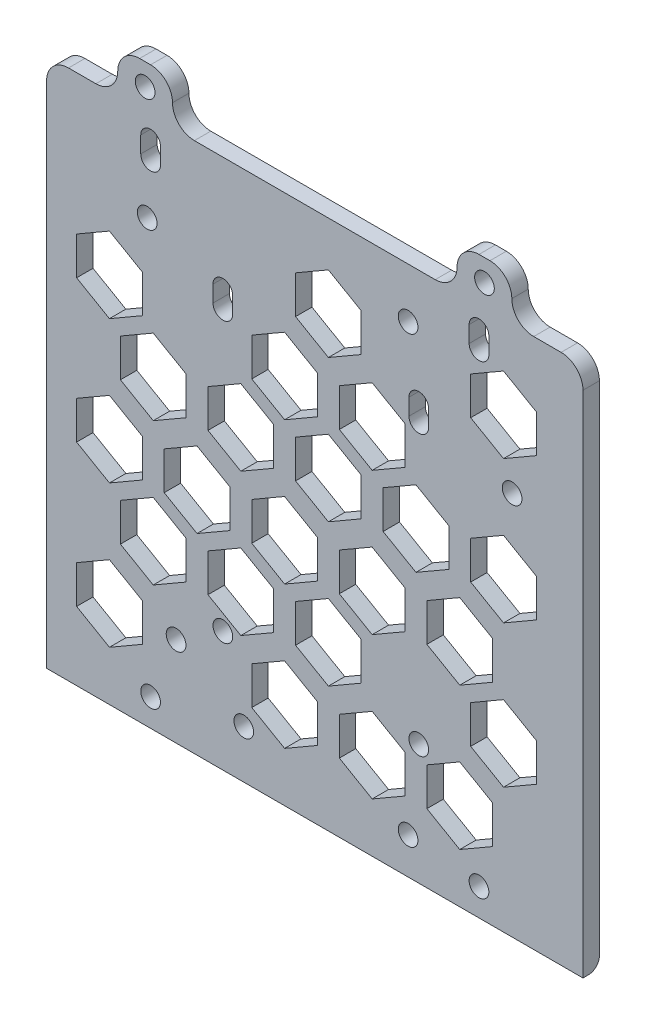
SolidWorks part; units mm, degrees
material "PLA 100% Infill"
ref_plane "Front Plane" through (0, 0, 0) normal (0, 0, 1) x (1, 0, 0)
ref_plane "Top Plane" through (0, 0, 0) normal (0, 1, 0) x (1, 0, 0)
ref_plane "Right Plane" through (0, 0, 0) normal (1, 0, 0) x (0, 0, -1)
sketch "Sketch1" plane through (0, 0, 0) normal (0, 0, 1) x (1, 0, 0)
  line L0 (-49, 97) -> (-49, 0) construction
  line L1 (0, 0) -> (-98, 0)
  line L2 (0, 0) -> (0, 97)
  line L3 (0, 97) -> (-98, 97)
  line L4 (-98, 0) -> (-98, 97)
  line L5 (-80, 101) -> (-18, 101) construction
  line L6 (-98, 97) -> (-75, 97)
  line L8 (-85, 105) -> (-75, 105)
  line L9 (-75, 97) -> (-75, 105)
  line L10 (0, 97) -> (-23, 97)
  line L12 (-13, 105) -> (-23, 105)
  line L13 (-23, 97) -> (-23, 105)
  line L14 (-80, 105) -> (-80, 101) construction
  line L15 (-85, 105) -> (-85, 97)
  line L16 (-80.8, 93) -> (-80.8, 90)
  line L17 (-13, 105) -> (-13, 97)
  line L18 (-18, 105) -> (-18, 101) construction
  line L19 (-77.2, 90) -> (-77.2, 93)
  line L20 (-20.8, 90) -> (-20.8, 93)
  line L21 (-17.2, 93) -> (-17.2, 90)
  line L22 (-19, 91.5) -> (-19, 5) construction
  line L23 (-30, 22) -> (-65.8, 22) construction
  line L24 (-65.8, 76) -> (-65.8, 22) construction
  line L25 (-30, 76) -> (-30, 22) construction
  line L26 (-67.6, 76) -> (-67.6, 73)
  line L27 (-64, 76) -> (-64, 73)
  line L28 (-31.8, 76) -> (-31.8, 73)
  line L29 (-28.2, 76) -> (-28.2, 73)
  circle A0 centre (-79, 5) radius 1.8
  circle A1 centre (-19, 5) radius 1.8
  circle A2 centre (-19, 91.5) radius 1.8
  circle A3 centre (-79, 91.5) radius 1.8
  circle A4 centre (-80, 101) radius 1.8
  circle A5 centre (-18, 101) radius 1.8
  arc A6 (-80.8, 90) -> (-77.2, 90) centre (-79, 90) ccw
  arc A7 (-77.2, 93) -> (-80.8, 93) centre (-79, 93) ccw
  arc A8 (-17.2, 90) -> (-20.8, 90) centre (-19, 90) cw
  arc A9 (-20.8, 93) -> (-17.2, 93) centre (-19, 93) cw
  circle A10 centre (-30, 22) radius 1.8
  circle A11 centre (-65.8, 22) radius 1.8
  circle A12 centre (-65.8, 76) radius 1.8
  circle A13 centre (-30, 76) radius 1.8
  circle A14 centre (-65.8, 73) radius 1.8
  circle A15 centre (-30, 73) radius 1.8
  point P61 (0, 0)
  point P62 (-64, 73)
  point P63 (0, 0)
  point P64 (-28.2, 73)
  point P65 (-30, 76.446)
  dimension "D5" = 3.6
  dimension "D8" = 86.5
  dimension "D9" = 10
  dimension "D10" = 8
  dimension "D4" = 5
  dimension "D11" = 62
  dimension "D12" = 62
  dimension "D15" = 4
  dimension "D16" = 60
  dimension "D17" = 3.6
  dimension "D1" = 98
  dimension "D2" = 97
  dimension "D3" = 60
  dimension "D13" = 1.5
  dimension "D14" = 3
  dimension "D18" = 35.8
  dimension "D19" = 30
  dimension "D20" = 22
  dimension "D22" = 3
  dimension "D23" = 54
  dimension "D6" = 2
  dimension "D7" = 2
  dimension "D21" = 2
extrude "Boss-Extrude1" add sketch "Sketch1" along normal blind 3 contours L3 L9 L8 A4 | L4 L1 L2 L3 A3 A2 A1 A0 | L13 L3 L12 A5 region at (-49.0073, 48.3433, 0) region at (-18, 97.1281, 0) region at (-84.8719, 101, 0)
fillet "Fillet1" radius 4 10 edges at (0, 97, 1.5) (-13, 97, 1.5) (-13, 105, 1.5) (-23, 105, 1.5) (-23, 97, 1.5) (-75, 97, 1.5) (-75, 105, 1.5) (-98, 97, 1.5) (-85, 105, 1.5) (-85, 97, 1.5)
fillet "Fillet2" radius 2 1 edges at (-49, 0, 0)
sketch "Sketch3" plane through (0, 0, 3) normal (0, 0, 1) x (1, 0, 0)
  line L0 (-98, 0) -> (-98, 93) construction
  line L1 (-80.5172, 12.537) -> (-80.5172, 19.4652)
  line L2 (-80.5172, 19.4652) -> (-86.5172, 22.9293)
  line L3 (-86.5172, 22.9293) -> (-92.5172, 19.4652)
  line L4 (-92.5172, 19.4652) -> (-92.5172, 12.537)
  line L5 (-92.5172, 12.537) -> (-86.5172, 9.0729)
  line L6 (-86.5172, 9.0729) -> (-80.5172, 12.537)
  line L14 (-72.5172, 26.3934) -> (-72.5172, 33.3216)
  line L15 (-72.5172, 33.3216) -> (-78.5172, 36.7857)
  line L16 (-78.5172, 36.7857) -> (-84.5172, 33.3216)
  line L17 (-84.5172, 33.3216) -> (-84.5172, 26.3934)
  line L18 (-84.5172, 26.3934) -> (-78.5172, 22.9293)
  line L19 (-78.5172, 22.9293) -> (-72.5172, 26.3934)
  line L25 (-56.5172, 26.3934) -> (-56.5172, 33.3216)
  line L26 (-56.5172, 33.3216) -> (-62.5172, 36.7857)
  line L27 (-62.5172, 36.7857) -> (-68.5172, 33.3216)
  line L28 (-68.5172, 33.3216) -> (-68.5172, 26.3934)
  line L29 (-68.5172, 26.3934) -> (-62.5172, 22.9293)
  line L30 (-62.5172, 22.9293) -> (-56.5172, 26.3934)
  line L31 (-48.5172, 12.537) -> (-48.5172, 19.4652)
  line L32 (-48.5172, 19.4652) -> (-54.5172, 22.9293)
  line L33 (-54.5172, 22.9293) -> (-60.5172, 19.4652)
  line L34 (-60.5172, 19.4652) -> (-60.5172, 12.537)
  line L35 (-60.5172, 12.537) -> (-54.5172, 9.0729)
  line L36 (-54.5172, 9.0729) -> (-48.5172, 12.537)
  line L37 (-40.5172, 26.3934) -> (-40.5172, 33.3216)
  line L38 (-40.5172, 33.3216) -> (-46.5172, 36.7857)
  line L39 (-46.5172, 36.7857) -> (-52.5172, 33.3216)
  line L40 (-52.5172, 33.3216) -> (-52.5172, 26.3934)
  line L41 (-52.5172, 26.3934) -> (-46.5172, 22.9293)
  line L42 (-46.5172, 22.9293) -> (-40.5172, 26.3934)
  line L43 (-32.5172, 12.537) -> (-32.5172, 19.4652)
  line L44 (-32.5172, 19.4652) -> (-38.5172, 22.9293)
  line L45 (-38.5172, 22.9293) -> (-44.5172, 19.4652)
  line L46 (-44.5172, 19.4652) -> (-44.5172, 12.537)
  line L47 (-44.5172, 12.537) -> (-38.5172, 9.0729)
  line L48 (-38.5172, 9.0729) -> (-32.5172, 12.537)
  line L55 (-16.5172, 12.537) -> (-16.5172, 19.4652)
  line L56 (-16.5172, 19.4652) -> (-22.5172, 22.9293)
  line L57 (-22.5172, 22.9293) -> (-28.5172, 19.4652)
  line L58 (-28.5172, 19.4652) -> (-28.5172, 12.537)
  line L59 (-28.5172, 12.537) -> (-22.5172, 9.0729)
  line L60 (-22.5172, 9.0729) -> (-16.5172, 12.537)
  line L61 (-8.5172, 26.3934) -> (-8.5172, 33.3216)
  line L62 (-8.5172, 33.3216) -> (-14.5172, 36.7857)
  line L63 (-14.5172, 36.7857) -> (-20.5172, 33.3216)
  line L64 (-20.5172, 33.3216) -> (-20.5172, 26.3934)
  line L65 (-20.5172, 26.3934) -> (-14.5172, 22.9293)
  line L66 (-14.5172, 22.9293) -> (-8.5172, 26.3934)
  line L67 (-64.5172, 38.537) -> (-64.5172, 45.4652)
  line L68 (-64.5172, 45.4652) -> (-70.5172, 48.9293)
  line L69 (-70.5172, 48.9293) -> (-76.5172, 45.4652)
  line L70 (-76.5172, 45.4652) -> (-76.5172, 38.537)
  line L71 (-76.5172, 38.537) -> (-70.5172, 35.0729)
  line L72 (-70.5172, 35.0729) -> (-64.5172, 38.537)
  line L73 (-56.5172, 52.3934) -> (-56.5172, 59.3216)
  line L74 (-56.5172, 59.3216) -> (-62.5172, 62.7857)
  line L75 (-62.5172, 62.7857) -> (-68.5172, 59.3216)
  line L76 (-68.5172, 59.3216) -> (-68.5172, 52.3934)
  line L77 (-68.5172, 52.3934) -> (-62.5172, 48.9293)
  line L78 (-62.5172, 48.9293) -> (-56.5172, 52.3934)
  line L79 (-48.5172, 38.537) -> (-48.5172, 45.4652)
  line L80 (-48.5172, 45.4652) -> (-54.5172, 48.9293)
  line L81 (-54.5172, 48.9293) -> (-60.5172, 45.4652)
  line L82 (-60.5172, 45.4652) -> (-60.5172, 38.537)
  line L83 (-60.5172, 38.537) -> (-54.5172, 35.0729)
  line L84 (-54.5172, 35.0729) -> (-48.5172, 38.537)
  line L85 (-40.5172, 52.3934) -> (-40.5172, 59.3216)
  line L86 (-40.5172, 59.3216) -> (-46.5172, 62.7857)
  line L87 (-46.5172, 62.7857) -> (-52.5172, 59.3216)
  line L88 (-52.5172, 59.3216) -> (-52.5172, 52.3934)
  line L89 (-52.5172, 52.3934) -> (-46.5172, 48.9293)
  line L90 (-46.5172, 48.9293) -> (-40.5172, 52.3934)
  line L91 (-32.5172, 38.537) -> (-32.5172, 45.4652)
  line L92 (-32.5172, 45.4652) -> (-38.5172, 48.9293)
  line L93 (-38.5172, 48.9293) -> (-44.5172, 45.4652)
  line L94 (-44.5172, 45.4652) -> (-44.5172, 38.537)
  line L95 (-44.5172, 38.537) -> (-38.5172, 35.0729)
  line L96 (-38.5172, 35.0729) -> (-32.5172, 38.537)
  line L97 (-24.5172, 52.3934) -> (-24.5172, 59.3216)
  line L98 (-24.5172, 59.3216) -> (-30.5172, 62.7857)
  line L99 (-30.5172, 62.7857) -> (-36.5172, 59.3216)
  line L100 (-36.5172, 59.3216) -> (-36.5172, 52.3934)
  line L101 (-36.5172, 52.3934) -> (-30.5172, 48.9293)
  line L102 (-30.5172, 48.9293) -> (-24.5172, 52.3934)
  line L103 (-16.5172, 38.537) -> (-16.5172, 45.4652)
  line L104 (-16.5172, 45.4652) -> (-22.5172, 48.9293)
  line L105 (-22.5172, 48.9293) -> (-28.5172, 45.4652)
  line L106 (-28.5172, 45.4652) -> (-28.5172, 38.537)
  line L107 (-28.5172, 38.537) -> (-22.5172, 35.0729)
  line L108 (-22.5172, 35.0729) -> (-16.5172, 38.537)
  line L109 (-8.5172, 52.3934) -> (-8.5172, 59.3216)
  line L110 (-8.5172, 59.3216) -> (-14.5172, 62.7857)
  line L111 (-14.5172, 62.7857) -> (-20.5172, 59.3216)
  line L112 (-20.5172, 59.3216) -> (-20.5172, 52.3934)
  line L113 (-20.5172, 52.3934) -> (-14.5172, 48.9293)
  line L114 (-14.5172, 48.9293) -> (-8.5172, 52.3934)
  line L127 (-48.5172, 64.537) -> (-48.5172, 71.4652)
  line L128 (-48.5172, 71.4652) -> (-54.5172, 74.9293)
  line L129 (-54.5172, 74.9293) -> (-60.5172, 71.4652)
  line L130 (-60.5172, 71.4652) -> (-60.5172, 64.537)
  line L131 (-60.5172, 64.537) -> (-54.5172, 61.0729)
  line L132 (-54.5172, 61.0729) -> (-48.5172, 64.537)
  line L133 (-40.5172, 78.3934) -> (-40.5172, 85.3216)
  line L134 (-40.5172, 85.3216) -> (-46.5172, 88.7857)
  line L135 (-46.5172, 88.7857) -> (-52.5172, 85.3216)
  line L136 (-52.5172, 85.3216) -> (-52.5172, 78.3934)
  line L137 (-52.5172, 78.3934) -> (-46.5172, 74.9293)
  line L138 (-46.5172, 74.9293) -> (-40.5172, 78.3934)
  line L139 (-32.5172, 64.537) -> (-32.5172, 71.4652)
  line L140 (-32.5172, 71.4652) -> (-38.5172, 74.9293)
  line L141 (-38.5172, 74.9293) -> (-44.5172, 71.4652)
  line L142 (-44.5172, 71.4652) -> (-44.5172, 64.537)
  line L143 (-44.5172, 64.537) -> (-38.5172, 61.0729)
  line L144 (-38.5172, 61.0729) -> (-32.5172, 64.537)
  line L157 (-8.5172, 78.3934) -> (-8.5172, 85.3216)
  line L158 (-8.5172, 85.3216) -> (-14.5172, 88.7857)
  line L159 (-14.5172, 88.7857) -> (-20.5172, 85.3216)
  line L160 (-20.5172, 85.3216) -> (-20.5172, 78.3934)
  line L161 (-20.5172, 78.3934) -> (-14.5172, 74.9293)
  line L162 (-14.5172, 74.9293) -> (-8.5172, 78.3934)
  line L163 (-80.5172, 38.537) -> (-80.5172, 45.4652)
  line L164 (-80.5172, 45.4652) -> (-86.5172, 48.9293)
  line L165 (-86.5172, 48.9293) -> (-92.5172, 45.4652)
  line L166 (-92.5172, 45.4652) -> (-92.5172, 38.537)
  line L167 (-92.5172, 38.537) -> (-86.5172, 35.0729)
  line L168 (-86.5172, 35.0729) -> (-80.5172, 38.537)
  line L169 (-72.5172, 52.3934) -> (-72.5172, 59.3216)
  line L170 (-72.5172, 59.3216) -> (-78.5172, 62.7857)
  line L171 (-78.5172, 62.7857) -> (-84.5172, 59.3216)
  line L172 (-84.5172, 59.3216) -> (-84.5172, 52.3934)
  line L173 (-84.5172, 52.3934) -> (-78.5172, 48.9293)
  line L174 (-78.5172, 48.9293) -> (-72.5172, 52.3934)
  line L175 (-80.5172, 64.537) -> (-80.5172, 71.4652)
  line L176 (-80.5172, 71.4652) -> (-86.5172, 74.9293)
  line L177 (-86.5172, 74.9293) -> (-92.5172, 71.4652)
  line L178 (-92.5172, 71.4652) -> (-92.5172, 64.537)
  line L179 (-92.5172, 64.537) -> (-86.5172, 61.0729)
  line L180 (-86.5172, 61.0729) -> (-80.5172, 64.537)
  line L187 (-56.5172, 85.3216) -> (-62.5172, 88.7857) [skipped]
  line L188 (-68.5172, 78.3934) -> (-62.5172, 74.9293) [skipped]
  line L189 (-64.5172, 71.4652) -> (-70.5172, 74.9293) [skipped]
  line L190 (-76.5172, 64.537) -> (-70.5172, 61.0729) [skipped]
  line L191 (-70.5172, 61.0729) -> (-64.5172, 64.537) [skipped]
  line L192 (-64.5172, 64.537) -> (-64.5172, 71.4652) [skipped]
  line L193 (-70.5172, 74.9293) -> (-76.5172, 71.4652) [skipped]
  line L194 (-76.5172, 71.4652) -> (-76.5172, 64.537) [skipped]
  line L195 (-62.5172, 88.7857) -> (-68.5172, 85.3216) [skipped]
  line L196 (-72.5172, 78.3934) -> (-72.5172, 85.3216) [skipped]
  line L197 (-84.5172, 85.3216) -> (-84.5172, 78.3934) [skipped]
  line L198 (-78.5172, 88.7857) -> (-84.5172, 85.3216) [skipped]
  line L199 (-72.5172, 85.3216) -> (-78.5172, 88.7857) [skipped]
  line L200 (-84.5172, 78.3934) -> (-78.5172, 74.9293) [skipped]
  line L201 (-78.5172, 74.9293) -> (-72.5172, 78.3934) [skipped]
  line L202 (-68.5172, 85.3216) -> (-68.5172, 78.3934) [skipped]
  line L203 (-62.5172, 74.9293) -> (-56.5172, 78.3934) [skipped]
  line L204 (-56.5172, 78.3934) -> (-56.5172, 85.3216) [skipped]
  line L205 (-36.5172, 78.3934) -> (-30.5172, 74.9293) [skipped]
  line L206 (-24.5172, 78.3934) -> (-24.5172, 85.3216) [skipped]
  line L207 (-30.5172, 88.7857) -> (-36.5172, 85.3216) [skipped]
  line L208 (-36.5172, 85.3216) -> (-36.5172, 78.3934) [skipped]
  line L209 (-24.5172, 85.3216) -> (-30.5172, 88.7857) [skipped]
  line L210 (-30.5172, 74.9293) -> (-24.5172, 78.3934) [skipped]
  line L211 (-64.5172, 19.4652) -> (-70.5172, 22.9293) [skipped]
  line L212 (-64.5172, 12.537) -> (-64.5172, 19.4652) [skipped]
  line L213 (-36.5172, 26.3934) -> (-30.5172, 22.9293) [skipped]
  line L214 (-30.5172, 22.9293) -> (-24.5172, 26.3934) [skipped]
  line L215 (-24.5172, 23.3102) -> (-24.5172, 33.3216) [skipped]
  line L216 (-24.5172, 33.3216) -> (-30.5172, 36.7857) [skipped]
  line L217 (-30.5172, 36.7857) -> (-36.5172, 33.3216) [skipped]
  line L218 (-36.5172, 33.3216) -> (-36.5172, 26.3934) [skipped]
  line L219 (-70.5172, 9.0729) -> (-64.5172, 12.537) [skipped]
  line L220 (-76.5172, 12.537) -> (-70.5172, 9.0729) [skipped]
  line L221 (-76.5172, 19.4652) -> (-76.5172, 12.537) [skipped]
  line L222 (-70.5172, 22.9293) -> (-76.5172, 19.4652) [skipped]
  line L223 (-22.5172, 74.9293) -> (-28.5172, 71.4652) [skipped]
  line L224 (-28.5172, 71.4652) -> (-28.5172, 64.537) [skipped]
  line L225 (-22.5172, 61.0729) -> (-16.5172, 64.537) [skipped]
  line L226 (-16.5172, 64.537) -> (-16.5172, 71.4652) [skipped]
  line L227 (-16.5172, 71.4652) -> (-22.5172, 74.9293) [skipped]
  line L228 (-28.5172, 64.537) -> (-22.5172, 61.0729) [skipped]
  circle A0 centre (-86.5172, 16.0011) radius 6 construction
  circle A2 centre (-78.5172, 29.8575) radius 6 construction
  point P10 (-75.5172, 24.6614)
  dimension "D1" = 12
  dimension "D2" = 12
  dimension "D3" = 4
  dimension "D4" = 2
  dimension "D5" = 5
  dimension "D6" = 3
extrude "Cut-Extrude1" cut sketch "Sketch3" against normal through all
sketch "Sketch4" plane through (0, 0, 3) normal (0, 0, 1) x (1, 0, 0)
  circle A0 centre (-74.3438, 16.37) radius 1.8
  circle A1 centre (-61.9736, 8.8272) radius 1.8
  circle A2 centre (-31.9533, 6.6831) radius 1.8
  circle A3 centre (-12.9454, 70.2256) radius 1.8
  circle A4 centre (-31.9533, 87.8757) radius 1.8
  circle A5 centre (-79.6238, 80.4838) radius 1.8
  dimension "D1" = 3.6
extrude "Cut-Extrude2" cut sketch "Sketch4" against normal through all
